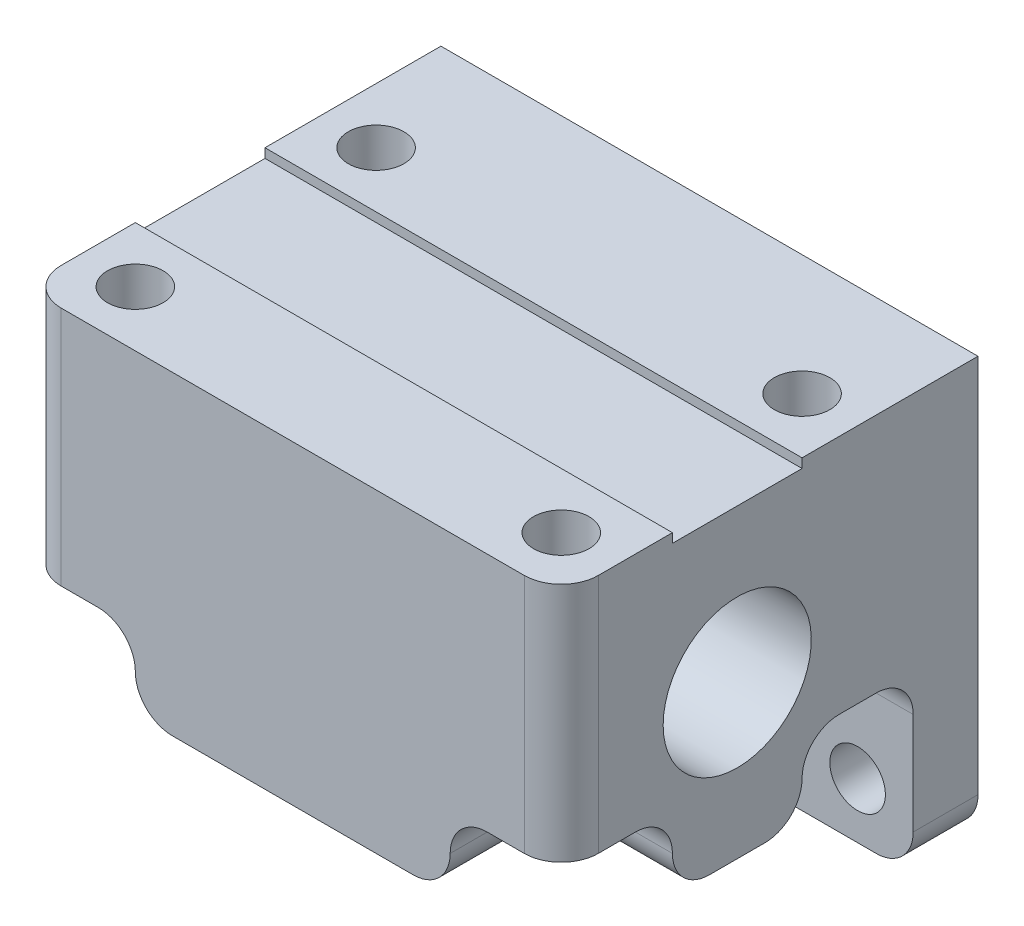
SolidWorks part; units mm, degrees
ref_plane "Front Plane" through (0, 0, 0) normal (0, 0, 1) x (1, 0, 0)
ref_plane "Top Plane" through (0, 0, 0) normal (0, 1, 0) x (1, 0, 0)
ref_plane "Right Plane" through (0, 0, 0) normal (1, 0, 0) x (0, 0, -1)
sketch "Sketch1" plane through (0, 0, 0) normal (0, 0, 1) x (1, 0, 0)
  line L0 (0, 0) -> (29, 0)
  line L1 (29, 0) -> (29, 22.5)
  line L2 (29, 22.5) -> (0, 22.5)
  line L3 (0, 22.5) -> (0, 0)
  dimension "D1" = 29
  dimension "D2" = 22.5
extrude "Boss-Extrude1" add sketch "Sketch1" along normal blind 3.5
sketch "Sketch2" plane through (0, 0, 3.5) normal (0, 0, 1) x (1, 0, 0)
  line L0 (0, 22.5) -> (0, 5.5)
  line L1 (0, 22.5) -> (0, 0) construction
  line L2 (0, 5.5) -> (29, 5.5)
  line L3 (29, 0) -> (29, 22.5) construction
  line L4 (29, 5.5) -> (29, 22.5)
  line L5 (29, 22.5) -> (0, 22.5)
  dimension "D1" = 17
extrude "Boss-Extrude2" add sketch "Sketch2" along normal blind 19
sketch "Sketch3" plane through (0, 0, 0) normal (-1, 0, 0) x (0, 0, 1)
  line L0 (3.5, 5.5) -> (3.5, 22.5) construction
  line L1 (22.5, 22.5) -> (0, 22.5) construction
  line L2 (3.5, 5.5) -> (22.5, 5.5) construction
  line L3 (13, 5.5) -> (13, 9.75) construction
  line L4 (13, 9.75) -> (13, 17.75) construction
  line L5 (13, 17.75) -> (13, 22) construction
  line L6 (13, 22) -> (13, 22.5) construction
  line L12 (13, 22) -> (9.5, 22)
  line L13 (9.5, 22) -> (9.5, 22.5)
  line L14 (9.5, 22.5) -> (16.5, 22.5)
  line L15 (16.5, 22.5) -> (16.5, 22)
  line L16 (16.5, 22) -> (13, 22)
  circle A0 centre (13, 13.75) radius 4
  dimension "D1" = 0.5
  dimension "D2" = 8
  dimension "D3" = 7
extrude "Cut-Extrude1" cut sketch "Sketch3" against normal up to surface (29 mm away) up to face at (29, 9.3333, 8.6667)
sketch "Sketch4" plane through (0, 5.5, 0) normal (0, -1, 0) x (1, 0, 0)
  line L0 (0, 22.5) -> (0, 16.5) construction
  line L1 (0, 16.5) -> (6, 22.5) construction
  line L2 (0, 22.5) -> (29, 22.5) construction
  line L3 (6, 22.5) -> (0, 22.5) construction
  line L4 (29, 22.5) -> (29, 16.5) construction
  line L5 (29, 22.5) -> (29, 3.5) construction
  line L6 (29, 16.5) -> (23, 22.5) construction
  line L7 (23, 22.5) -> (29, 22.5) construction
  line L8 (0, 3.5) -> (6, 3.5) construction
  line L9 (0, 3.5) -> (29, 3.5) construction
  line L10 (6, 3.5) -> (0, 9.5) construction
  line L11 (0, 22.5) -> (0, 3.5) construction
  line L12 (0, 9.5) -> (0, 3.5) construction
  line L13 (29, 3.5) -> (29, 9.5) construction
  line L14 (29, 9.5) -> (23, 3.5) construction
  line L15 (23, 3.5) -> (29, 3.5) construction
  circle A0 centre (3, 19.5) radius 1.5
  circle A1 centre (26, 19.5) radius 1.5
  circle A2 centre (26, 6.5) radius 1.5
  circle A3 centre (3, 6.5) radius 1.5
  dimension "D2" = 3
  dimension "D1" = 6
extrude "Cut-Extrude2" cut sketch "Sketch4" against normal up to surface (17 mm away) up to face at (14.5, 22.5, 19.5)
sketch "Sketch5" plane through (0, 0, 3.5) normal (0, 0, 1) x (1, 0, 0)
  line L0 (0, 0) -> (0, 6) construction
  line L1 (0, 5.5) -> (0, 0) construction
  line L2 (0, 6) -> (6, 0) construction
  line L3 (0, 0) -> (29, 0) construction
  line L4 (6, 0) -> (0, 0) construction
  line L5 (29, 0) -> (29, 6) construction
  line L6 (29, 0) -> (29, 5.5) construction
  line L7 (29, 6) -> (23, 0) construction
  line L8 (23, 0) -> (29, 0) construction
  circle A0 centre (3, 3) radius 1.5
  circle A1 centre (26, 3) radius 1.5
  dimension "D2" = 3
  dimension "D1" = 6
extrude "Cut-Extrude3" cut sketch "Sketch5" against normal up to surface (3.5 mm away) up to face at (14.5, 11.25, 0)
sketch "Sketch6" plane through (0, 5.5, 0) normal (0, -1, 0) x (1, 0, 0)
  line L0 (0, 22.5) -> (6, 22.5)
  line L1 (0, 22.5) -> (29, 22.5) construction
  line L2 (6, 22.5) -> (6, 16.5)
  line L3 (6, 16.5) -> (0, 16.5)
  line L4 (0, 22.5) -> (0, 3.5) construction
  line L5 (0, 16.5) -> (0, 22.5)
  line L6 (29, 22.5) -> (23, 22.5)
  line L7 (23, 22.5) -> (23, 16.5)
  line L8 (23, 16.5) -> (29, 16.5)
  line L9 (29, 22.5) -> (29, 3.5) construction
  line L10 (29, 16.5) -> (29, 22.5)
  line L11 (29, 3.5) -> (23, 3.5)
  line L12 (29, 3.5) -> (29, 0) construction
  line L13 (0, 3.5) -> (29, 3.5) construction
  line L14 (23, 3.5) -> (23, 9.5)
  line L15 (23, 9.5) -> (29, 9.5)
  line L16 (29, 9.5) -> (29, 3.5)
  line L17 (0, 3.5) -> (6, 3.5)
  line L18 (6, 3.5) -> (6, 9.5)
  line L19 (6, 9.5) -> (0, 9.5)
  line L20 (0, 9.5) -> (0, 3.5)
  dimension "D1" = 6
extrude "Cut-Extrude4" cut sketch "Sketch6" against normal blind 4
fillet "Fillet1" radius 2 20 edges at (29, 0, 1.75) (0, 0, 1.75) (29, 16, 22.5) (0, 16, 22.5) (6, 5.5, 6.5) (6, 9.5, 6.5) (3, 5.5, 9.5) (3, 9.5, 9.5) (3, 5.5, 16.5) (3, 9.5, 16.5) (6, 5.5, 19.5) (6, 9.5, 19.5) (23, 5.5, 6.5) (23, 9.5, 6.5) (26, 9.5, 9.5) (26, 5.5, 9.5) (23, 5.5, 19.5) (26, 5.5, 16.5) (26, 9.5, 16.5) (23, 9.5, 19.5)
fillet "Fillet4" radius 2 7 edges at (2, 9.5, 3.5) (5.4142, 8.9142, 3.5) (6.5858, 6.0858, 3.5) (27, 9.5, 3.5) (23.5858, 8.9142, 3.5) (22.4142, 6.0858, 3.5) (14.5, 5.5, 3.5)
equation "\"board_length\"= 260mm"
equation "\"board_height\"= 200mm"
equation "\"board_width\"= 16.5mm"
equation "\"token_thickness\"= 7mm"
equation "\"token_diameter\"= 32mm"
equation "\"board_side_lower_height\"= 55mm"
equation "\"board_side_height\"= 156.5mm"
equation "\"board_side_length\"= 100mm"
equation "\"board_slot_width\"= \"board_length\" / 7"
equation "\"token_ridge\"= ( \"token_thickness\" - 4mm ) / 2"
equation "\"token_ridge_width\"= 1.5mm"
equation "\"25T_outer_diameter\"= 20mm"
equation "\"25T_inner_diameter\"= 9mm"
equation "\"2T_screw_distance\"= 14mm"
equation "\"2T_outer_thickness\"= 2mm"
equation "\"2T_inner_thickness\"= 4.5mm"
equation "\"MG996R_outer_length\"= 54mm"
equation "\"MG996R_inner_length\"= 40mm"
equation "\"MG996R_width\"= 20mm"
equation "\"MG996R_height\"= 26.6mm"
equation "\"MG996R_full_height\"= 45.7mm"
equation "\"MG996R_full_width\"= 55.5mm"
equation "\"MG996R_screw_distance\"= 10mm"
equation "\"magnet_diameter\"= 10mm"
equation "\"magnet_thickness\"= 2mm"
equation "\"dispenser_barrel_margin\"= 2.5mm"
equation "\"dispenser_wheel_width\"= \"token_thickness\" + 5mm"
equation "\"dispenser_cover_margin\"= 3.0mm"
equation "\"dispenser_cover_thickness\"= 5.0mm"
equation "\"MG996R_major_axis_distance\"= 34.3mm"
equation "\"MG996R_major_screw_distance\"= 48.6mm"
equation "\"MG996R_minor_screw_distance\"= 9.9mm"
equation "\"MG996R_mid_height\"= 37.5mm"
equation "\"dispenser_slope\"= 30deg"
equation "\"dispenser_cover_length\"= 16mm"
equation "\"dispenser_carrier_width\"= 3.5mm"
equation "\"dispenser_carrier_height\"= 50mm"
equation "\"carrier_width\"= \"shaft_diameter\" * 2"
equation "\"shaft_diameter\"= 8mm"
equation "\"carrier_thickness\"=16mm"
equation "\"GT2_width\"= 7mm"
equation "\"GT2_outer_diameter\"= 18mm"
equation "\"GT2_inner_diameter\"= 12mm"
equation "\"GT2_pitch_diameter\"= 2mm"
equation "\"GT2_tooth_height\"= 1.6mm"
equation "\"GT2_upper_length\"= 0.6mm"
equation "\"belt_holder_width\"= \"GT2_width\" + 2 * 6mm"
equation "\"carrier_screw_distance\"= \"dispenser_cover_thickness\" + 3 * 6mm"
equation "\"D1@Sketch1\"=\"carrier_screw_distance\"+6mm"
equation "\"D2@Sketch1\"=\"carrier_height_top\""
equation "\"D1@Boss-Extrude1\"=\"dispenser_carrier_width\""
equation "\"D1@Sketch2\"=\"dispenser_cover_length\"+\"GT2_pitch_diameter\"/2"
equation "\"D1@Boss-Extrude2\"=\"GT2_width\"+2*6mm"
equation "\"D2@Sketch3\"=\"shaft_diameter\""
equation "\"D3@Sketch3\"=\"GT2_width\""
equation "\"magnetometer_offset\"= 6mm"
equation "\"magnetometer_width\"= 15mm"
equation "\"magnetometer_length\"= 19mm"
equation "\"magnetometer_thickness\" = 2.5mm"
equation "\"timing_belt_gap\"= 2.5mm"
equation "\"carrier_height_top\"= 6mm + \"carrier_thickness\" + 0.5mm"
equation "\"carrier_height_bot\"= 6mm + \"carrier_thickness\" + \"GT2_inner_diameter\" + 1.0mm + \"timing_belt_gap\""
